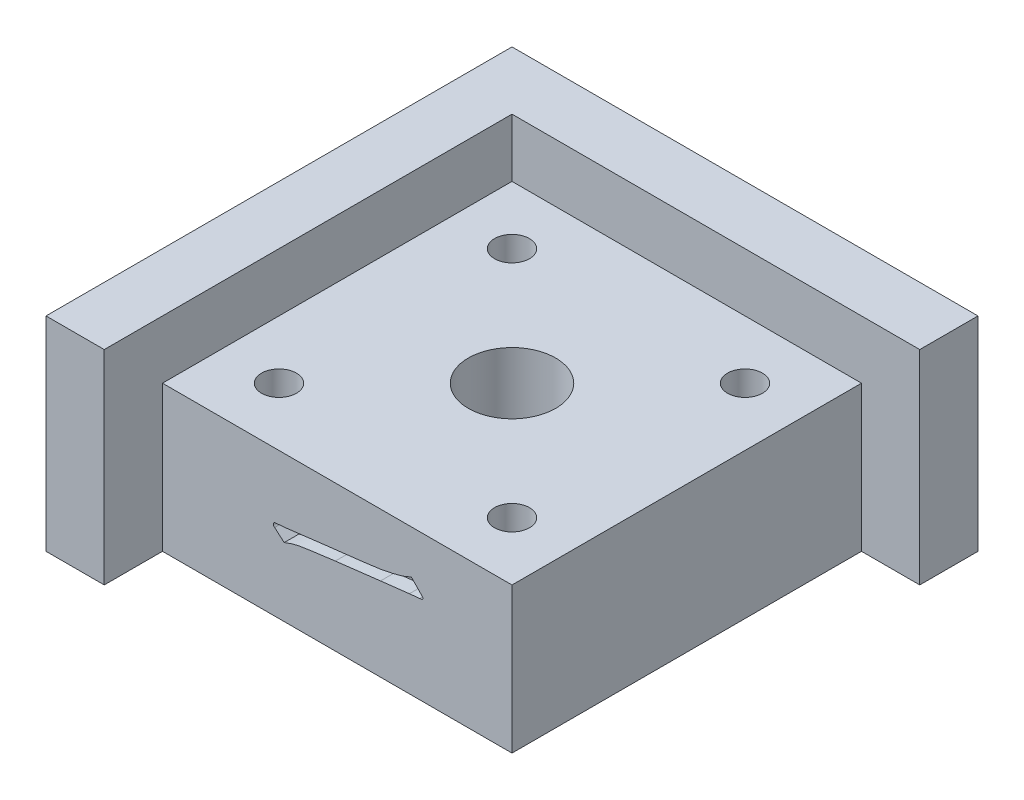
SolidWorks part; units mm, degrees
ref_plane "前视基准面" through (0, 0, 0) normal (0, 0, 1) x (1, 0, 0)
ref_plane "上视基准面" through (0, 0, 0) normal (0, 1, 0) x (1, 0, 0)
ref_plane "右视基准面" through (0, 0, 0) normal (1, 0, 0) x (0, 0, -1)
sketch "Sketch1" plane through (0, 0, 0) normal (0, 1, 0) x (1, 0, 0)
  line L0 (6, 0) -> (6, -6) construction
  line L1 (0, 0) -> (12, 0)
  line L2 (0, 0) -> (0, -12)
  line L3 (0, -12) -> (12, -12)
  line L4 (12, 0) -> (12, -12)
extrude "Boss-Extrude1" add sketch "Sketch1" against normal blind 3
shell "Shell2" thickness 1.8 removed face at (6, -3, 6)
sketch "Sketch3" plane through (0, 0, 0) normal (0, 1, 0) x (1, 0, 0)
  line L0 (0, 0) -> (0, 2) construction
  line L1 (0, 2) -> (-2, 2) construction
  line L2 (6, 2) -> (6, -6) construction
  line L3 (-2, 2) -> (14, 2)
  line L4 (-2, 2) -> (-2, -14)
  line L5 (-2, -14) -> (14, -14)
  line L6 (14, 2) -> (14, -14)
  circle A0 centre (6, -6) radius 1.5
  line M6 (0, 0) -> (0, -12)
  line M7 (0, -12) -> (12, -12)
  line M8 (12, -12) -> (12, 0)
  line M9 (12, 0) -> (0, 0)
extrude "Cut-Extrude3" cut sketch "Sketch3" against normal up to surface (1.8 mm away) contours A0 region at (6, 0, 6) up to face at (6, -1.8, 6)
extrude "Boss-Extrude2" add sketch "Sketch3<3>" along normal blind 2 contours A0 M9 M6 M7 M8 | L6 L3 L4 L5 M6 M9 M8 M7 region at (6, 0, -1.7737) region at (6, 0, 0.1697)
sketch "Sketch3<3>" plane through (0, 0, 0) normal (0, 1, 0) x (1, 0, 0) same geometry as "Sketch3"
sketch "Sketch4" plane through (0, 2, 0) normal (0, 1, 0) x (1, 0, 0)
  line L0 (-2, -14) -> (14, -14) construction
  line L1 (-2, 2) -> (0, 2)
  line L2 (-2, 2) -> (-2, -14)
  line L3 (-2, -14) -> (0, -14)
  line L4 (0, 2) -> (0, -14)
  line L5 (14, 2) -> (14, -14) construction
  line L6 (0, 2) -> (14, 2)
  line L7 (0, 2) -> (0, 0)
  line L8 (0, 0) -> (14, 0)
  line L9 (14, 2) -> (14, 0)
  line M10 (14, -14) -> (14, 2)
  line M11 (14, 2) -> (-2, 2)
  line M12 (-2, 2) -> (-2, -14)
  line M13 (-2, -14) -> (14, -14)
extrude "Boss-Extrude3" add sketch "Sketch4" along normal blind 2 contours L4 M11 M12 M13 | L4 L8 M10 M11 region at (-1, 2, 6) region at (7, 2, -1)
sketch "Sketch5" plane through (0, 0, 0) normal (0, -1, 0) x (1, 0, 0)
  line L1 (14, 14) -> (-2, 14)
  line L2 (14, 14) -> (14, -2)
  line L3 (14, -2) -> (-2, -2)
  line L4 (-2, 14) -> (-2, -2)
  line L5 (12, 12) -> (0, 12)
  line L6 (12, 12) -> (12, 0)
  line L7 (12, 0) -> (0, 0)
  line L8 (0, 12) -> (0, 0)
extrude "Boss-Extrude4" add sketch "Sketch5" along normal up to surface (3 mm away) up to face at (6, -3, 6)
sketch "Sketch6" plane through (0, 0, 14) normal (0, 0, 1) x (1, 0, 0)
  line L0 (-2, -3) -> (14, -3) construction
  line L1 (14, 2) -> (0, 2)
  line L2 (14, 2) -> (14, -3)
  line L3 (14, -3) -> (0, -3)
  line L4 (0, 2) -> (0, -3)
extrude "Cut-Extrude4" cut sketch "Sketch6" against normal blind 2
sketch "Sketch7" plane through (14, 0, 0) normal (1, 0, 0) x (0, 0, -1)
  line L1 (0, 2) -> (-12, 2)
  line L2 (0, 2) -> (0, -3)
  line L3 (0, -3) -> (-12, -3)
  line L4 (-12, 2) -> (-12, -3)
extrude "Cut-Extrude5" cut sketch "Sketch7" against normal blind 2
sketch "Sketch8" plane through (0, 0, 12) normal (0, 0, 1) x (1, 0, 0)
  text T0 " 一"
extrude "Cut-Extrude6" cut sketch "Sketch8" against normal blind 0.5
sketch "Sketch9" plane through (0, 2, 0) normal (0, 1, 0) x (1, 0, 0)
  line L0 (0, -12) -> (2, -12) construction
  line L1 (12, -12) -> (0, -12) construction
  line L2 (2, -12) -> (2, -10) construction
  line L3 (12, -12) -> (10, -12) construction
  line L4 (10, -12) -> (10, -10) construction
  line L5 (0, 0) -> (2, 0) construction
  line L6 (0, 0) -> (14, 0) construction
  line L7 (2, 0) -> (2, -2) construction
  line L8 (12, 0) -> (10, 0) construction
  line L9 (10, 0) -> (10, -2) construction
  circle A0 centre (2, -10) radius 0.6
  circle A1 centre (2, -10) radius 0.6054
  circle A2 centre (10, -10) radius 0.6
  circle A3 centre (2, -2) radius 0.6
  circle A4 centre (10, -2) radius 0.6
extrude "Cut-Extrude7" cut sketch "Sketch9" against normal up to surface (3.8 mm away) contours A2 | A3 | A4 | A0 up to face at (6, -1.8, 7.5)
